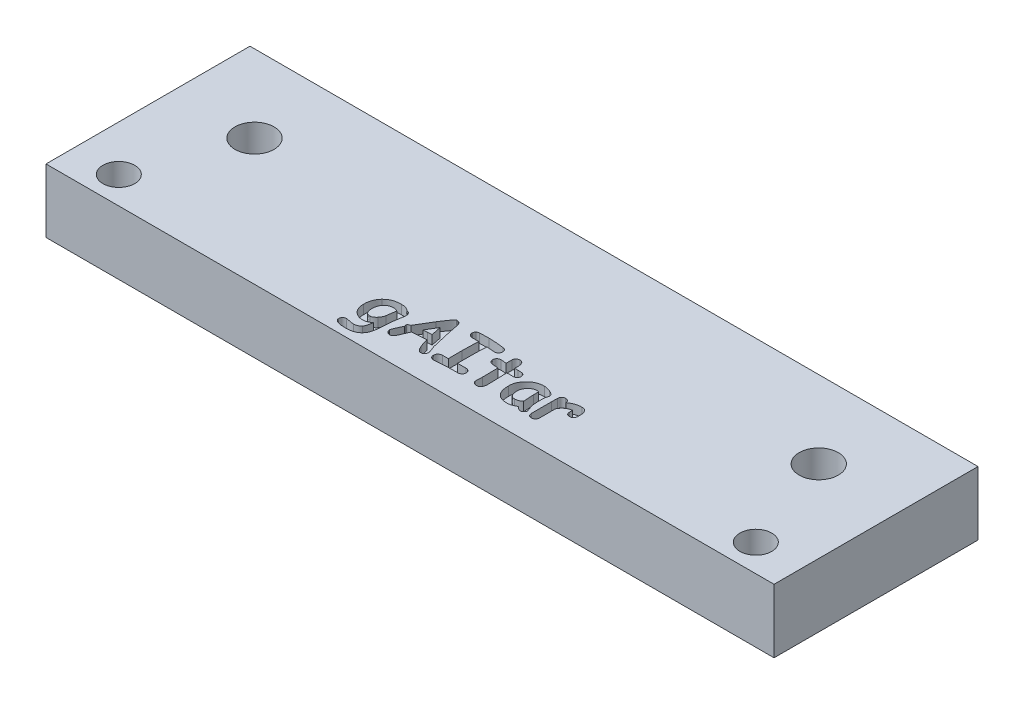
SolidWorks part; units mm, degrees
ref_plane "Front Plane" through (0, 0, 0) normal (0, 0, 1) x (1, 0, 0)
ref_plane "Top Plane" through (0, 0, 0) normal (0, 1, 0) x (1, 0, 0)
ref_plane "Right Plane" through (0, 0, 0) normal (1, 0, 0) x (0, 0, -1)
sketch "Sketch1" plane through (0, 0, 0) normal (0, 1, 0) x (1, 0, 0)
  line L0 (-5.2629, -14.8686) -> (74.7371, -14.8686)
  line L1 (74.7371, -14.8686) -> (74.7371, -37.2808)
  line L2 (-5.2629, -14.8686) -> (13.6704, -14.8686)
  line L3 (63.3564, -14.8686) -> (74.7371, -14.8686)
  line L4 (74.7371, -37.2808) -> (-5.2629, -37.2808)
  line L5 (-5.2629, -30.8686) -> (-5.2629, -37.2808)
  line L6 (-5.2629, -30.8686) -> (-5.2629, -14.8686)
  line L7 (-5.2629, -23.3686) -> (74.7371, -23.3686) construction
  line L8 (-0.2629, -14.8686) -> (-0.2629, -53.6929) construction
  line L9 (69.7371, -53.6929) -> (69.7371, -14.8686) construction
  line L11 (-5.2629, -30.8686) -> (74.7371, -30.8686) construction
  circle A0 centre (-0.2629, -34.2808) radius 1.75
  circle A1 centre (69.7371, -34.2808) radius 1.75
  circle A2 centre (3.7371, -23.3686) radius 2.15
  circle A3 centre (65.7371, -23.3686) radius 2.15
  dimension "D6" = 62
  dimension "D1" = 3
  dimension "D2" = 8.5
  dimension "D3" = 5
  dimension "D4" = 16
  dimension "D5" = 3
  dimension "D7" = 9
  dimension "D8" = 9
extrude "Boss-Extrude1" add sketch "Sketch1" against normal blind 7 contours L3 A1 | L2 A0 region at (34.7371, 0, 26.0292)
sketch "Sketch2" plane through (0, 0, 0) normal (0, 1, 0) x (1, 0, 0)
  text T0 "<b>gAItar</b>" font "Comic Sans MS" height in points 18
extrude "Cut-Extrude1" cut sketch "Sketch2" against normal blind 1
